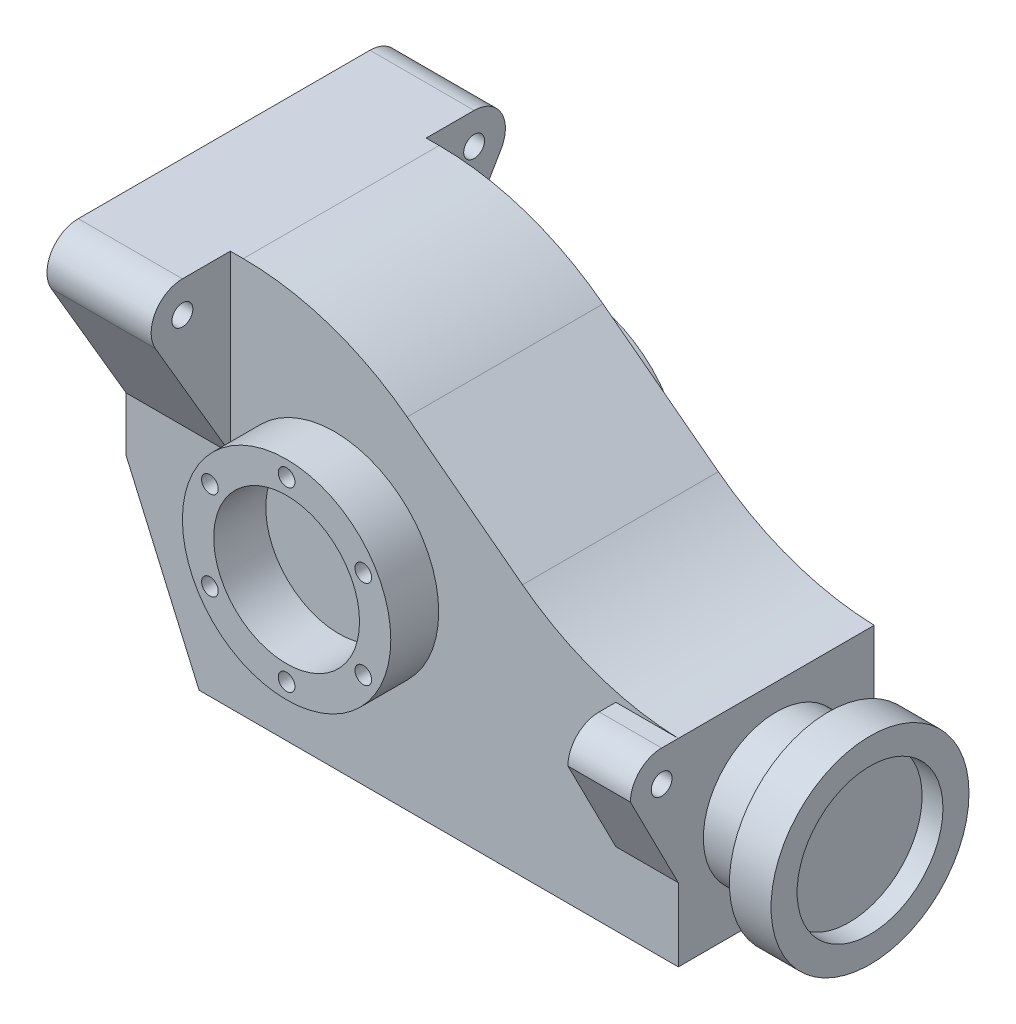
SolidWorks part; units mm, degrees
ref_plane "Płaszczyzna przednia" through (0, 0, 0) normal (0, 0, 1) x (1, 0, 0)
ref_plane "Płaszczyzna górna" through (0, 0, 0) normal (0, 1, 0) x (1, 0, 0)
ref_plane "Płaszczyzna prawa" through (0, 0, 0) normal (1, 0, 0) x (0, 0, -1)
sketch "Szkic1" plane through (0, 0, 0) normal (0, 0, 1) x (1, 0, 0)
  line L0 (-35, 190) -> (65, 190)
  line L1 (65, 190) -> (190, 95)
  line L2 (190, 95) -> (230, 95)
  line L3 (230, 95) -> (230, 0)
  line L4 (230, 0) -> (0, 0)
  line L7 (-35, 190) -> (-35, 80)
  line L8 (-35, 80) -> (0, 0)
  dimension "D1" = 265
  dimension "D2" = 190
  dimension "D3" = 95
  dimension "D4" = 80
  dimension "D5" = 230
  dimension "D6" = 100
  dimension "D7" = 40
extrude "Dodanie-wyciągnięcie1" add sketch "Szkic1" along normal mid plane 94 contours L1 L2 L3 L4 L8 L7 L0
sketch "Szkic2" plane through (230, 0, 0) normal (1, 0, 0) x (0, 0, -1)
  line L0 (-47, 95) -> (47, 0) construction
  line L1 (47, 95) -> (-47, 0) construction
  line L2 (-47, 0) -> (47, 0) construction
  circle A0 centre (0, 47.5) radius 35
  point P13 (0, 47.5)
  dimension "D1" = 70
extrude "Dodanie-wyciągnięcie2" add sketch "Szkic2" along normal blind 25 separate body
sketch "Szkic3" plane through (255, 0, 0) normal (1, 0, 0) x (0, 0, -1)
  circle A0 centre (0, 47.5) radius 47.5
  circle A1 centre (0, 47.5) radius 35 construction
  dimension "D1" = 95
extrude "Dodanie-wyciągnięcie3" add sketch "Szkic3" along normal blind 20
sketch "Szkic4" plane through (275, 0, 0) normal (1, 0, 0) x (0, 0, -1)
  circle A0 centre (0, 47.5) radius 35
  circle A1 centre (0, 47.5) radius 47.5 construction
  dimension "D1" = 70
sketch "Szkic7" plane through (0, 0, 47) normal (0, 0, 1) x (1, 0, 0)
  line L0 (-35, 190) -> (-35, 80) construction
  line L1 (-35, 190) -> (65, 190) construction
  circle A0 centre (65, 90) radius 50
  dimension "D1" = 100
  dimension "D2" = 100
  dimension "D3" = 100
extrude "Dodanie-wyciągnięcie5" add sketch "Szkic7" along normal blind 23
sketch "Szkic8" plane through (0, 0, 70) normal (0, 0, 1) x (1, 0, 0)
  circle A0 centre (65, 90) radius 35
  dimension "D1" = 70
extrude "Wytnij-wyciągnięcie1" cut sketch "Szkic8" against normal blind 25
sketch "Szkic9" plane through (0, 0, 70) normal (0, 0, 1) x (1, 0, 0)
  line L0 (65, 90) -> (65, 132.5) construction
  circle A0 centre (65, 132.5) radius 4
  circle A1 centre (101.8061, 111.25) radius 4
  circle A2 centre (65, 90) radius 35 construction
  circle A3 centre (65, 90) radius 35
  circle A4 centre (101.8061, 68.75) radius 4
  circle A5 centre (65, 47.5) radius 4
  circle A6 centre (28.1939, 68.75) radius 4
  circle A7 centre (28.1939, 111.25) radius 4
  dimension "D1" = 8
  dimension "D2" = 42.5
  dimension "D3" = 6
  dimension "D4" = 42.5
extrude "Wytnij-wyciągnięcie2" cut sketch "Szkic9" against normal blind 15 contours A0 | A1 | A4 | A5 | A6 | A7
sketch "Szkic12" plane through (-35, 0, 0) normal (-1, 0, 0) x (0, 0, 1)
  line L0 (-70, 190) -> (70, 190)
  line L1 (47, 190) -> (-47, 190) construction
  line L2 (-82.9419, 167.4166) -> (-20, 60)
  line L4 (47, 0) -> (-47, 0) construction
  line L5 (-20, 60) -> (20, 60)
  line L6 (0, 190) -> (0, 60) construction
  line L7 (82.9419, 167.4166) -> (20, 60)
  circle A0 centre (-70, 175) radius 5
  arc A1 (-70, 190) -> (-82.9419, 167.4166) centre (-70, 175) ccw
  arc A2 (70, 190) -> (82.9419, 167.4166) centre (70, 175) cw
  circle A3 centre (70, 175) radius 5
  line M4 (-47, 190) -> (-47, 80)
  line M5 (-47, 80) -> (47, 80)
  line M6 (47, 80) -> (47, 190)
  line M7 (47, 190) -> (-47, 190)
  dimension "D1" = 10
  dimension "D2" = 30
  dimension "D4" = 20
  dimension "D5" = 70
  dimension "D3" = 60
extrude "Dodanie-wyciągnięcie6" add sketch "Szkic12" against normal blind 50 contours L0 A1 L2 A0 M4 | L6 L0 L2 M4 M5 | L6 L7 M7 M5 M6 | A2 L0 L7 A3 M6 | L6 L5 L7 M5 | L6 L2 L5 M5 region at (-35, 159.5519, -61.1328) region at (-35, 136.8562, -22.7622) region at (-35, 136.8562, 22.7622) region at (-35, 159.5519, 61.1328) region at (-35, 70.7553, 13.1511) region at (-35, 70.7553, -13.1511)
mirror "Lustro1" about plane through (0, 0, 0) normal (0, 0, 1) of "Wytnij-wyciągnięcie2", "Wytnij-wyciągnięcie1", "Dodanie-wyciągnięcie5"
fillet "Zaokrąglenie2" radius 130 1 edges at (65, 190, 0)
fillet "Zaokrąglenie3" radius 130 1 edges at (190, 95, 0)
extrude "Wytnij-wyciągnięcie3" cut sketch "Szkic4" against normal blind 10
sketch "Szkic13" plane through (0, 0, 47) normal (0, 0, 1) x (1, 0, 0)
  line L0 (230, 95) -> (230, 0) construction
  line L1 (230, 95) -> (200, 95)
  line L2 (230, 95) -> (230, 35)
  line L3 (230, 35) -> (200, 35)
  line L4 (200, 95) -> (200, 35)
  dimension "D1" = 60
  dimension "D2" = 30
sketch "Szkic14" plane through (0, 0, 70) normal (0, 0, 1) x (1, 0, 0)
  line L1 (200, 95) -> (230, 95)
  line L2 (200, 95) -> (200, 60)
  line L3 (200, 60) -> (230, 60)
  line L4 (230, 95) -> (230, 60)
  line L5 (230, 95) -> (230, 35) construction
  dimension "D1" = 35
loft "Wyciągnięcie po profilach1" add profiles "Szkic13", "Szkic14" connector at (230, 35, 47) connector at (230, 60, 70)
sketch "Szkic15" plane through (230, 0, 0) normal (1, 0, 0) x (0, 0, -1)
  line L0 (-47, 95) -> (-70, 95) construction
  line L1 (-70, 60) -> (-70, 95) construction
  line L5 (-70, 80) -> (-70, 95)
  line L6 (-70, 95) -> (-55, 95)
  arc A0 (-55, 95) -> (-70, 80) centre (-55, 80) ccw
  dimension "D1" = 30
extrude "Wytnij-wyciągnięcie4" cut sketch "Szkic15" against normal up to next (30 mm away)
sketch "Szkic19" plane through (230, 0, 0) normal (1, 0, 0) x (0, 0, -1)
  line L0 (-70, 80) -> (-47, 35)
  line L1 (-47, 35) -> (-70, 60)
  line L2 (-70, 60) -> (-70, 80)
extrude "Wytnij-wyciągnięcie6" cut sketch "Szkic19" against normal up to next (30 mm away) contours L0 L1 L2
sketch "Szkic20" plane through (230, 0, 0) normal (1, 0, 0) x (0, 0, -1)
  circle A0 centre (-55, 80) radius 5
  arc A1 (-55, 95) -> (-70, 80) centre (-55, 80) ccw construction
  dimension "D1" = 10
extrude "Wytnij-wyciągnięcie7" cut sketch "Szkic20" against normal up to next (30 mm away)
